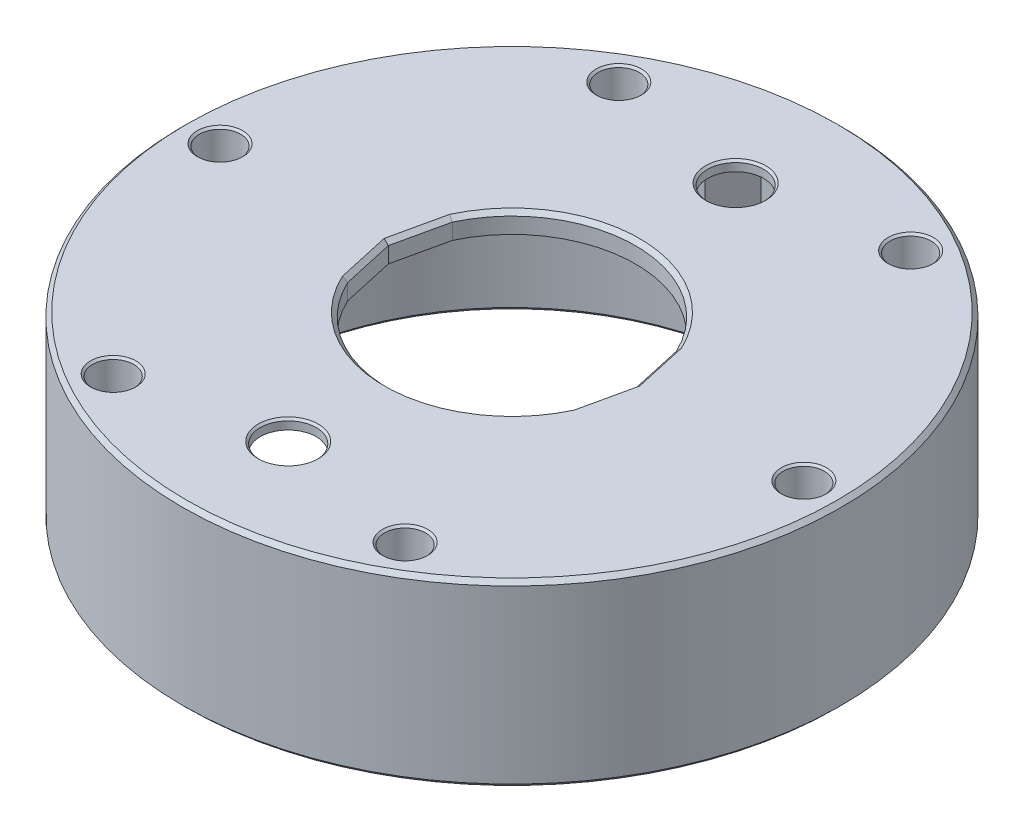
SolidWorks part; units mm, degrees
ref_plane "Front Plane" through (0, 0, 0) normal (0, 0, 1) x (1, 0, 0)
ref_plane "Top Plane" through (0, 0, 0) normal (0, 1, 0) x (1, 0, 0)
ref_plane "Right Plane" through (0, 0, 0) normal (1, 0, 0) x (0, 0, -1)
sketch "Sketch1" plane through (0, 0, 0) normal (0, 1, 0) x (1, 0, 0)
  circle A0 centre (0, 0) radius 12.73
  circle A1 centre (0, 0) radius 16.5
  dimension "D1" = 3.77
  dimension "D2" = 33
extrude "Boss-Extrude1" add sketch "Sketch1" along normal blind 8
sketch "Sketch2" plane through (0, 8, 0) normal (0, 1, 0) x (1, 0, 0)
  circle A0 centre (0, 0) radius 16.5
extrude "Boss-Extrude2" add sketch "Sketch2" along normal blind 1
sketch "Sketch3" plane through (0, 9, 0) normal (0, 1, 0) x (1, 0, 0)
  line L0 (0, 13) -> (0, 11.2)
  line L1 (0, -13) -> (0, -11.2)
  line L2 (0, -13) -> (3.3, -13)
  line L3 (0, -13) -> (-3.3, -13)
  line L4 (0, 13) -> (-3.3, 13)
  line L5 (0, 13) -> (3.3, 13)
  line L6 (-6.1875, 0) -> (-3.3, -13)
  line L7 (6.1875, 0) -> (3.3, -13)
  line L8 (-3.3, 13) -> (-6.1875, 0)
  line L9 (3.3, 13) -> (6.1875, 0)
  circle A0 centre (0, 0) radius 6.1875
  circle A4 centre (0, 11.2) radius 1.4025
  circle A5 centre (0, -11.2) radius 1.4025
  dimension "D1" = 12.375
  dimension "D7" = 1.8
  dimension "D8" = 2.805
  dimension "D9" = 1.8
  dimension "D10" = 2.805
  dimension "D2" = 13
  dimension "D3" = 13
  dimension "D4" = 3.3
  dimension "D5" = 3.3
  dimension "D6" = 3.3
  dimension "D11" = 3.3
extrude "Cut-Extrude1" cut sketch "Sketch3" against normal blind 12 contours L9 A0 L8 L6 L7 | A4 | A5 region at (0.9637, 9, -12.1637) region at (0, 9, 0) region at (-0.9637, 9, 10.2363)
sketch "Sketch4" plane through (0, 8, 0) normal (0, -1, 0) x (1, 0, 0)
  line L1 (3.4641, 11.2) -> (1.7321, 14.2)
  line L2 (1.7321, 14.2) -> (-1.7321, 14.2)
  line L3 (-1.7321, 14.2) -> (-3.4641, 11.2)
  line L4 (-3.4641, 11.2) -> (-1.7321, 8.2)
  line L5 (-1.7321, 8.2) -> (1.7321, 8.2)
  line L6 (1.7321, 8.2) -> (3.4641, 11.2)
  circle A0 centre (0, 11.2) radius 3 construction
  dimension "D1" = 6
extrude "Cut-Extrude2" cut sketch "Sketch4" along normal blind 12
sketch "Sketch5" plane through (0, 8, 0) normal (0, -1, 0) x (1, 0, 0)
  line L1 (3.4416, 11.2) -> (1.7208, 14.1806)
  line L2 (1.7208, 14.1806) -> (-1.7208, 14.1806)
  line L3 (-1.7208, 14.1806) -> (-3.4416, 11.2)
  line L4 (-3.4416, 11.2) -> (-1.7208, 8.2194)
  line L5 (-1.7208, 8.2194) -> (1.7208, 8.2194)
  line L6 (1.7208, 8.2194) -> (3.4416, 11.2)
  circle A0 centre (0, 11.2) radius 2.9806 construction
extrude "Cut-Extrude3" cut sketch "Sketch5" against normal blind 0.5
sketch "Sketch6" plane through (0, 8, 0) normal (0, -1, 0) x (1, 0, 0)
  line L1 (3.4641, -11.2) -> (1.7321, -8.2)
  line L2 (1.7321, -8.2) -> (-1.7321, -8.2)
  line L3 (-1.7321, -8.2) -> (-3.4641, -11.2)
  line L4 (-3.4641, -11.2) -> (-1.7321, -14.2)
  line L5 (-1.7321, -14.2) -> (1.7321, -14.2)
  line L6 (1.7321, -14.2) -> (3.4641, -11.2)
  circle A0 centre (0, -11.2) radius 3 construction
  dimension "D1" = 6
extrude "Cut-Extrude4" cut sketch "Sketch6" along normal blind 17.5
sketch "Sketch7" plane through (0, 8, 0) normal (0, -1, 0) x (1, 0, 0)
  line L1 (3.4876, -11.2) -> (1.7438, -8.1797)
  line L2 (1.7438, -8.1797) -> (-1.7438, -8.1797)
  line L3 (-1.7438, -8.1797) -> (-3.4876, -11.2)
  line L4 (-3.4876, -11.2) -> (-1.7438, -14.2203)
  line L5 (-1.7438, -14.2203) -> (1.7438, -14.2203)
  line L6 (1.7438, -14.2203) -> (3.4876, -11.2)
  circle A0 centre (0, -11.2) radius 3.0203 construction
extrude "Cut-Extrude5" cut sketch "Sketch7" against normal blind 0.5
scale "Scale1" scale about centroid uniform scaling yes scale factor 1.212121
chamfer "Chamfer1" distance 0.25 angle 45 7 edges at (-7.1474, 9.8616, 1.5873) (-7.1474, 9.8616, -1.5878) (0, 9.8616, -7.5003) (7.1474, 9.8616, -1.5878) (7.1474, 9.8616, 1.5873) (0, 9.8616, 7.4997) (0, 9.8616, 19.9997)
chamfer "Chamfer2" distance 0.125 angle 45 2 edges at (0, 9.8616, -11.8761) (0, 9.8616, 15.2755)
chamfer "Chamfer3" distance 0.25 angle 45 8 edges at (2.7194, -1.0474, -16.1387) (0, -1.0474, -17.2124) (-2.7194, -1.0474, -16.1387) (-15.4303, -1.0474, -0.0003) (-2.7194, -1.0474, 16.1381) (0, -1.0474, 17.2118) (2.7194, -1.0474, 16.1381) (15.4303, -1.0474, -0.0003)
chamfer "Chamfer4" distance 0.25 angle 45 1 edges at (0, -1.0474, 19.9997)
sketch "Sketch8" plane through (0, 9.8616, 0) normal (0, 1, 0) x (1, 0, 0)
  line L3 (0, -6) -> (0, 6) construction
  line L5 (-6, 0) -> (6, 0) construction
  circle A0 centre (-17.7143, 0) radius 1.25
  circle A1 centre (17.7143, 0) radius 1.25
  circle A2 centre (-8.8571, -15.341) radius 1.25
  circle A3 centre (8.8571, 15.341) radius 1.25
  circle A5 centre (-8.8571, 15.341) radius 1.25
  circle A6 centre (8.8571, -15.341) radius 1.25
  dimension "D3" = 2.5
  dimension "D1" = 2.5
  dimension "D2" = 2.5
extrude "Cut-Extrude6" cut sketch "Sketch8" against normal through all
chamfer "Chamfer5" distance 0.125 angle 45 6 edges at (8.8571, 9.8616, -16.591) (17.7143, 9.8616, 1.25) (8.8571, 9.8616, 16.591) (-8.8571, 9.8616, 14.091) (-8.8571, 9.8616, -14.091) (-17.7143, 9.8616, 1.25)
